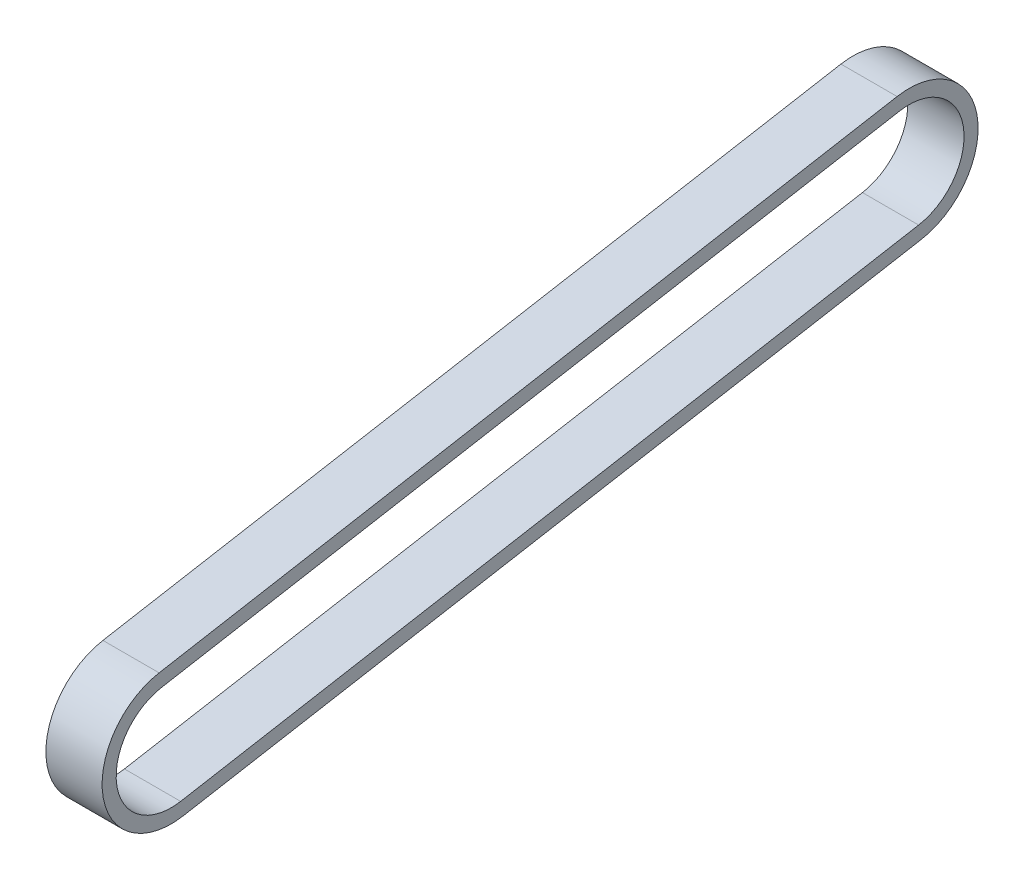
SolidWorks part; units mm, degrees
material "Rubber"
ref_plane "Front Plane" through (0, 0, 0) normal (0, 0, 1) x (1, 0, 0)
ref_plane "Top Plane" through (0, 0, 0) normal (0, 1, 0) x (1, 0, 0)
ref_plane "Right Plane" through (0, 0, 0) normal (1, 0, 0) x (0, 0, -1)
ref_plane "Plane2" through (-30.95, 0, 0) normal (-1, 0, 0) x (0, 0, 1)
ref_plane "Plane3" through (-37.95, 0, 0) normal (1, 0, 0) x (0, 0, -1)
ref_plane "Plane4" through (-34.45, 0, 0) normal (-1, 0, 0) x (0, 0, 1)
sketch "Sketch2" plane through (-34.45, 0, 0) normal (-1, 0, 0) x (0, 0, 1)
  line L0 (-40, 70) -> (38.7846, 56.1081) construction
  line L1 (-40, 70) -> (38.7846, 56.1081)
  line L2 (-40, 70) -> (38.7846, 56.1081) construction
  line L3 (-38.8946, 76.2693) -> (39.8901, 62.3774) construction
  line L4 (-41.1054, 63.7307) -> (37.6792, 49.8389) construction
  line L5 (-38.7209, 77.2541) -> (40.0637, 63.3622)
  line L6 (-41.2791, 62.7459) -> (37.5055, 48.8541)
  line L7 (-38.9814, 75.7769) -> (39.8032, 61.885)
  line L8 (-41.0186, 64.2231) -> (37.766, 50.3313)
  arc A0 (-38.8946, 76.2693) -> (-41.1054, 63.7307) centre (-40, 70) ccw construction
  arc A1 (37.6792, 49.8389) -> (39.8901, 62.3774) centre (38.7846, 56.1081) ccw construction
  arc A2 (37.5055, 48.8541) -> (40.0637, 63.3622) centre (38.7846, 56.1081) ccw
  arc A3 (-38.7209, 77.2541) -> (-41.2791, 62.7459) centre (-40, 70) ccw
  arc A4 (37.766, 50.3313) -> (39.8032, 61.885) centre (38.7846, 56.1081) ccw
  arc A5 (-38.9814, 75.7769) -> (-41.0186, 64.2231) centre (-40, 70) ccw
  point P2 (-0.6077, 63.0541)
  point P19 (-38.2743, 81.7564)
  dimension "D3" = 12.732
  dimension "D1" = 1
  dimension "D2" = 0.5
extrude "Boss-Extrude1" add sketch "Sketch2" along normal mid plane 6 contours L7 A5 L8 A4 | L5 A2 L6 A3 region at (-34.45, 67.9045, 0.2476)
